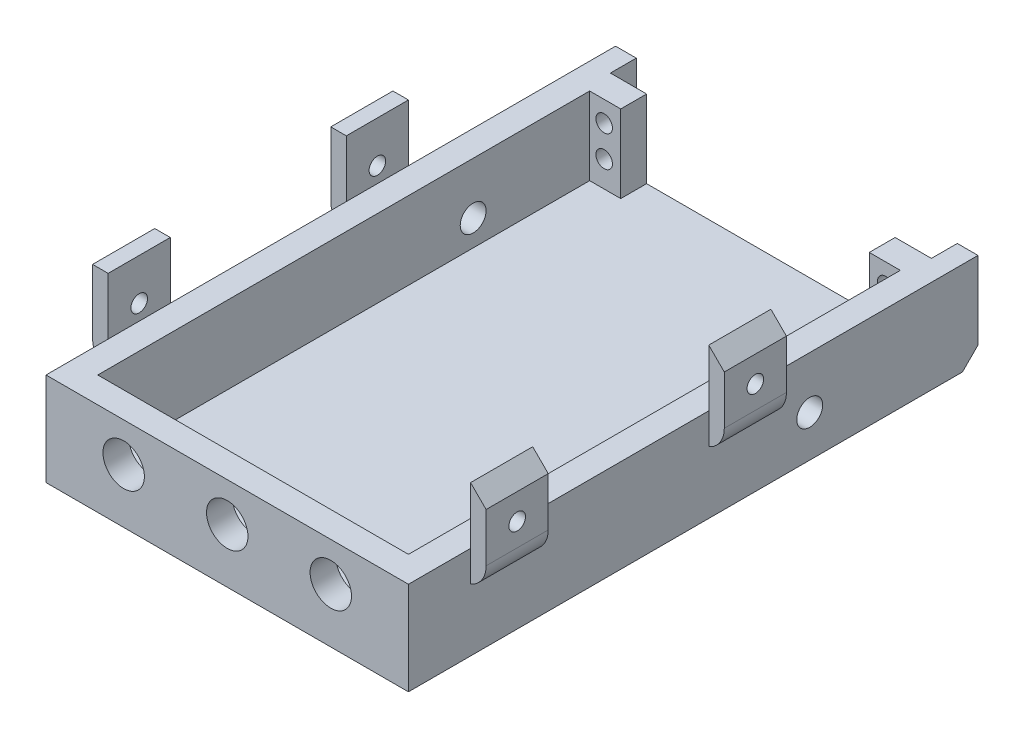
SolidWorks part; units mm, degrees
ref_plane "Alzado" through (0, 0, 0) normal (0, 0, 1) x (1, 0, 0)
ref_plane "Planta" through (0, 0, 0) normal (0, 1, 0) x (1, 0, 0)
ref_plane "Vista lateral" through (0, 0, 0) normal (1, 0, 0) x (0, 0, -1)
sketch "Croquis1" plane through (0, 0, 0) normal (0, 1, 0) x (1, 0, 0)
  line L1 (-35, 52.5) -> (35, 52.5)
  line L2 (-35, 52.5) -> (-35, -52.5)
  line L3 (-35, -52.5) -> (35, -52.5)
  line L4 (35, 52.5) -> (35, -52.5)
  line L5 (-35, 52.5) -> (35, -52.5) construction
  line L6 (-35, -52.5) -> (35, 52.5) construction
  point P0 (0, 0)
  dimension "D1" = 105
  dimension "D2" = 70
extrude "Saliente-Extruir1" add sketch "Croquis1" along normal blind 3
sketch "Croquis2" plane through (0, 3, 0) normal (0, 1, 0) x (1, 0, 0)
  line L1 (-35, 52.5) -> (-30, 52.5)
  line L2 (-35, 52.5) -> (-35, -52.5)
  line L4 (-30, 52.5) -> (-30, -47.5)
  line L5 (35, 52.5) -> (-35, 52.5) construction
  line L7 (35, -52.5) -> (35, 52.5)
  line L8 (35, 52.5) -> (30, 52.5)
  line L9 (30, -47.5) -> (30, 52.5)
  line L10 (-35, -52.5) -> (35, -52.5)
  line L12 (-30, -47.5) -> (30, -47.5)
  dimension "D1" = 5
  dimension "D2" = 5
  dimension "D3" = 100
  dimension "D4" = 100
extrude "Saliente-Extruir2" add sketch "Croquis2" along normal blind 15
ref_plane "Plano1" through (0, 0, -46.5) normal (0, 0, -1) x (-1, 0, 0)
sketch "Croquis10" plane through (35, 0, 0) normal (1, 0, 0) x (0, 0, -1)
  line L0 (11.5, 29) -> (11.5, 12) construction
  line L5 (-31.5, 18) -> (8.5, 18) construction
  line L10 (38.5, 0) -> (-38.5, 0) construction
  line L15 (8.5, 12) -> (17.5, 12)
  line L16 (8.5, 12) -> (8.5, 29)
  line L17 (8.5, 29) -> (17.5, 29)
  line L18 (17.5, 12) -> (17.5, 29)
  line L19 (-34.5, 12) -> (-28.5, 12)
  line L20 (11.5, 12) -> (5.5, 12)
  line L22 (11.5, 29) -> (5.5, 29)
  line L23 (5.5, 12) -> (5.5, 29)
  line L24 (-31.5, 12) -> (-40.5, 12)
  line L25 (-11.5, 11.4546) -> (-11.5, 24.5454)
  line L26 (52.5, 18) -> (52.5, 0) construction
  line L27 (-52.5, 18) -> (-52.5, 0) construction
  line L28 (-52.5, 0) -> (52.5, 0) construction
  line L29 (-40.5, 12) -> (-40.5, 29)
  line L30 (-34.5, 29) -> (-28.5, 29)
  line L31 (-31.5, 29) -> (-40.5, 29)
  line L32 (-28.5, 12) -> (-28.5, 29)
  circle A1 centre (11.5, 21) radius 1.6
  circle A2 centre (-34.5, 21) radius 1.6
  point P23 (8.5, 18)
  point P25 (-11.5, 18)
  point P26 (7.9335, 18)
  point P27 (0, 0)
  point P28 (8.5, 18)
  point P29 (7.535, 18)
  point P30 (0, 0)
  line M7 (52.5, 18) -> (-52.5, 18)
  dimension "D10" = 3.2
  dimension "D8" = 9
  dimension "D4" = 8
  dimension "D2" = 12
  dimension "D3" = 35
  dimension "D5" = 12
  dimension "D6" = 21
  dimension "D7" = 18
  dimension "D14" = 3
  dimension "D15" = 6
extrude "Saliente-Extruir4" add sketch "Croquis10" along normal blind 3 contours L18 L17 L16 A1 M7 | L15 L18 L16 M7 | L23 L20 L16 M7 | L23 L16 L22 M7 | L32 L30 L31 L29 A2 M7 | L19 L32 L29 L24 M7 region at (35, 15, -13) region at (35, 15, -7) region at (35, 15, 34.5) region at (35, 23.6622, 34.5) region at (35, 23.5, -7) region at (35, 23.7211, -13.1326)
fillet "Redondeo1" radius 5 2 edges at (38, 12, -11.5) (38, 12, 34.5)
mirror "Simetría1" about plane through (0, 0, 0) normal (1, 0, 0) of "Saliente-Extruir4", "Redondeo1"
sketch "Croquis12" plane through (-30, 0, 0) normal (1, 0, 0) x (0, 0, -1)
  line L0 (-47.5, 18) -> (52.5, 18) construction
  line L1 (47.5, 18) -> (52.5, 18)
  line L2 (47.5, 18) -> (47.5, 3)
  line L3 (47.5, 3) -> (52.5, 3)
  line L4 (52.5, 18) -> (52.5, 3)
  dimension "D1" = 5
extrude "Saliente-Extruir5" add sketch "Croquis12" along normal blind 6
mirror "Simetría2" about plane through (0, 0, 0) normal (1, 0, 0) of "Saliente-Extruir5"
sketch "Croquis13" plane through (0, 0, 52.5) normal (0, 0, 1) x (1, 0, 0)
  line L0 (-35, 0) -> (35, 0) construction
  line L2 (0, 10.5) -> (20, 10.5) construction
  line L3 (0, 10.5) -> (-20, 10.5) construction
  line L4 (0, 0) -> (0, 10.5) construction
  circle A0 centre (-20, 10.5) radius 4
  circle A1 centre (0, 10.5) radius 4
  circle A2 centre (20, 10.5) radius 4
  dimension "D1" = 8
  dimension "D2" = 8
  dimension "D3" = 8
  dimension "D4" = 10.5
  dimension "D5" = 20
  dimension "D6" = 20
extrude "Cortar-Extruir1" cut sketch "Croquis13" against normal up to next
sketch "Croquis14" plane through (0, 0, -52.5) normal (0, 0, -1) x (-1, 0, 0)
  line L0 (27.2, 14) -> (27.2, 8) construction
  line L2 (24, 18) -> (35, 18) construction
  line L3 (24, 3) -> (24, 18) construction
  circle A0 centre (27.2, 14) radius 1.6
  circle A1 centre (27.2, 8) radius 1.6
  dimension "D1" = 3.2
  dimension "D2" = 3.2
  dimension "D3" = 6
  dimension "D4" = 4
  dimension "D5" = 3.2
extrude "Cortar-Extruir2" cut sketch "Croquis14" against normal up to next
mirror "Simetría3" about plane through (0, 0, 0) normal (1, 0, 0) of "Cortar-Extruir2"
sketch "Croquis15" plane through (0, 0, -52.5) normal (0, 0, -1) x (-1, 0, 0)
  line L0 (-27.2, 14) -> (27.2, 14) construction
sketch "Croquis16" plane through (-35, 0, 0) normal (-1, 0, 0) x (0, 0, 1)
  line L0 (0, 0) -> (0, 8) construction
  line L1 (-52.5, 0) -> (52.5, 0) construction
  line L2 (0, 8) -> (-25, 8) construction
  circle A0 centre (-25, 8) radius 2.5
  dimension "D1" = 5
  dimension "D2" = 8
  dimension "D3" = 25
extrude "Cortar-Extruir3" cut sketch "Croquis16" against normal blind 70
sketch "Croquis17" plane through (0, 0, 0) normal (0, 1, 0) x (1, 0, 0)
  line L1 (35, 52.5) -> (31, 52.5)
  line L2 (35, 52.5) -> (35, 57.5)
  line L3 (35, 57.5) -> (31, 57.5)
  line L4 (31, 52.5) -> (31, 57.5)
extrude "Saliente-Extruir6" add sketch "Croquis17" along normal up to surface (18 mm away) up to face at (0, 18, -5.4)
mirror "Simetría4" about plane through (0, 0, 0) normal (1, 0, 0) of "Saliente-Extruir6"
chamfer "Chaflán1" distance 3 angle 45 2 edges at (-33, 0, -57.5) (33, 0, -57.5)
chamfer "Chaflán2" distance 3 angle 45 2 edges at (38, 29, -11.5) (38, 29, 34.5)
